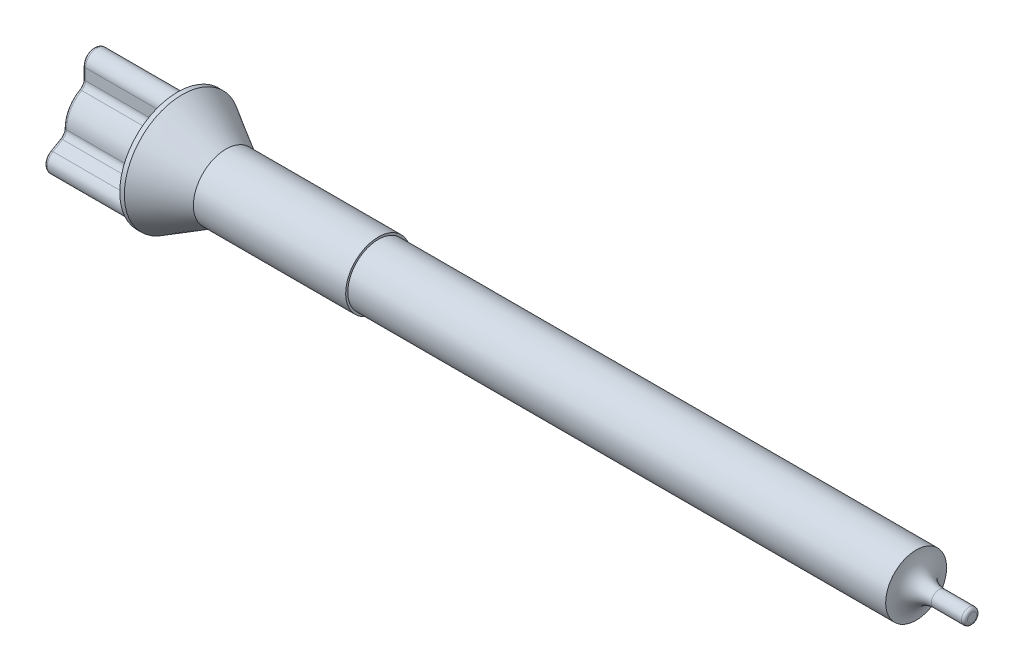
SolidWorks part; units mm, degrees
material "Berilyum S-65C, Vakumlu Sıcak Preslenmiş"
ref_plane "Ön Düzlem" through (0, 0, 0) normal (0, 0, 1) x (1, 0, 0)
ref_plane "Üst Düzlem" through (0, 0, 0) normal (0, 1, 0) x (1, 0, 0)
ref_plane "Sağ Düzlem" through (0, 0, 0) normal (1, 0, 0) x (0, 0, -1)
sketch "Çizim1" plane through (0, 0, 0) normal (0, 0, 1) x (1, 0, 0)
  line L0 (0, 0) -> (0, 1)
  line L1 (0, 1) -> (2.75, 1)
  line L2 (2.75, 1) -> (2.75, 1.9)
  line L3 (2.75, 1.9) -> (2.9, 1.9)
  line L4 (2.9, 1.9) -> (4.3376, 1.07)
  line L5 (4.3376, 1.07) -> (9.3376, 1.07)
  line L6 (9.3376, 1.07) -> (9.3376, 1)
  line L7 (9.3376, 1) -> (26.9976, 1)
  line L8 (26.9976, 1) -> (26.9976, 0)
  line L9 (26.9976, 0) -> (0, 0)
  dimension "D1" = 1
  dimension "D2" = 2.75
  dimension "D3" = 0.9
  dimension "D4" = 0.15
  dimension "D5" = 5
  dimension "D6" = 0.07
  dimension "D7" = 17.66
  dimension "D8" = 1
  dimension "D9" = 150
revolve "Döndür1" add sketch "Çizim1" angle 360 about L9
sketch "Çizim2" plane through (0, 0, 0) normal (-1, 0, 0) x (0, 0, 1)
  line L5 (-0.375, 0) -> (0.375, 0)
  line L6 (-0.375, 0) -> (-0.375, 1.45)
  line L7 (-0.375, 1.45) -> (0.375, 1.45) construction
  line L8 (0.375, 0) -> (0.375, 1.45)
  arc A0 (-0.375, 1.45) -> (0.375, 1.45) centre (0, 1.45) cw
  point P6 (0, 0)
  dimension "D1" = 0.75
  dimension "D2" = 1.45
extrude "Yükseklik-Ekstrüzyon1" add sketch "Çizim2" against normal up to surface (2.75 mm away) up to face at (2.75, 1, 0)
pattern_circular "Dairesel Kaplama1" count 3 over 360 about axis through (0, 0, 0) along (1, 0, 0) of "Yükseklik-Ekstrüzyon1"
fillet "Radyus1" radius 0.25 9 edges at (1.375, 0.927, -0.375) (1.375, -0.1388, -0.9903) (2.75, 0.5, -0.866) (1.375, -0.7883, -0.6153) (1.375, -0.7883, 0.6153) (2.75, -1, 0) (1.375, -0.1388, 0.9903) (1.375, 0.927, 0.375) (2.75, 0.5, 0.866)
sketch "Çizim3" plane through (26.9976, 0, 0) normal (1, 0, 0) x (0, 0, -1)
  circle A0 centre (0, 0) radius 0.25
  dimension "D1" = 0.5
extrude "Yükseklik-Ekstrüzyon2" add sketch "Çizim3" along normal blind 1.84
fillet "Radyus2" radius 0.75 1 edges at (26.9976, 0.25, 0)
fillet "Radyus3" radius 0.1 19 edges at (28.8376, 0.25, 0) (0, 1.825, 0) (0, 1.2663, -0.375) (0, -0.9125, -1.5805) (0, -0.9579, -0.9091) (0, -0.9125, 1.5805) (0, -0.3084, 1.2841) (0, 0.5, -0.866) (0, -0.3084, -1.2841) (0, -1, 0) (0, -0.9579, 0.9091) (0, 0.5, 0.866) (0, 1.2663, 0.375) (0, 0.9575, -0.4085) (0, -0.125, -1.0335) (0, -0.8325, -0.625) (0, -0.8325, 0.625) (0, -0.125, 1.0335) (0, 0.9575, 0.4085)
